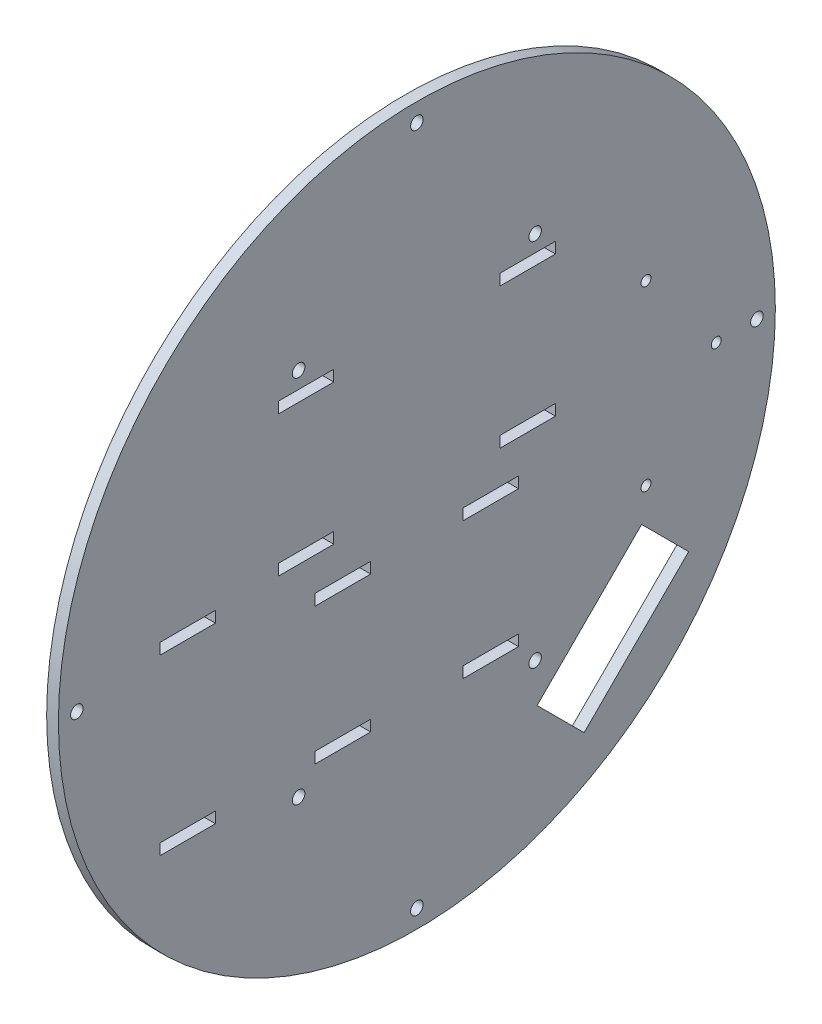
SolidWorks part; units mm, degrees
ref_plane "Front Plane" through (0, 0, 0) normal (0, 0, 1) x (1, 0, 0)
ref_plane "Top Plane" through (0, 0, 0) normal (0, 1, 0) x (1, 0, 0)
ref_plane "Right Plane" through (0, 0, 0) normal (1, 0, 0) x (0, 0, -1)
sketch "Tray Sketch" plane through (0, 0, 0) normal (1, 0, 0) x (0, 0, -1)
  line L0 (32.5269, -60.8112) -> (60.8112, -32.5269)
  line L1 (60.8112, -32.5269) -> (73.5391, -45.2548)
  line L2 (73.5391, -45.2548) -> (45.2548, -73.5391)
  line L3 (45.2548, -73.5391) -> (32.5269, -60.8112)
  line L4 (-22.5, 4.5) -> (-22.5, 7.5)
  line L5 (-22.5, 7.5) -> (-37.5, 7.5)
  line L6 (-37.5, 7.5) -> (-37.5, 4.5)
  line L7 (-37.5, 4.5) -> (-22.5, 4.5)
  line L8 (-22.5, 42.5) -> (-22.5, 45.5)
  line L9 (-22.5, 45.5) -> (-37.5, 45.5)
  line L10 (-37.5, 45.5) -> (-37.5, 42.5)
  line L11 (-37.5, 42.5) -> (-22.5, 42.5)
  line L12 (37.5, 4.5) -> (37.5, 7.5)
  line L13 (37.5, 7.5) -> (22.5, 7.5)
  line L14 (22.5, 7.5) -> (22.5, 4.5)
  line L15 (22.5, 4.5) -> (37.5, 4.5)
  line L16 (37.5, 42.5) -> (37.5, 45.5)
  line L17 (37.5, 45.5) -> (22.5, 45.5)
  line L18 (22.5, 45.5) -> (22.5, 42.5)
  line L19 (22.5, 42.5) -> (37.5, 42.5)
  line L20 (-12.5, -44.5) -> (-12.5, -41.5)
  line L21 (-12.5, -41.5) -> (-27.5, -41.5)
  line L22 (-27.5, -41.5) -> (-27.5, -44.5)
  line L23 (-27.5, -44.5) -> (-12.5, -44.5)
  line L24 (-12.5, -7.5) -> (-12.5, -4.5)
  line L25 (-12.5, -4.5) -> (-27.5, -4.5)
  line L26 (-27.5, -4.5) -> (-27.5, -7.5)
  line L27 (-27.5, -7.5) -> (-12.5, -7.5)
  line L28 (27.5, -44.5) -> (27.5, -41.5)
  line L29 (27.5, -41.5) -> (12.5, -41.5)
  line L30 (12.5, -41.5) -> (12.5, -44.5)
  line L31 (12.5, -44.5) -> (27.5, -44.5)
  line L32 (27.5, -7.5) -> (27.5, -4.5)
  line L33 (27.5, -4.5) -> (12.5, -4.5)
  line L34 (12.5, -4.5) -> (12.5, -7.5)
  line L35 (12.5, -7.5) -> (27.5, -7.5)
  line L36 (-54.5, -45) -> (-54.5, -42)
  line L37 (-54.5, -42) -> (-69.5, -42)
  line L38 (-69.5, -42) -> (-69.5, -45)
  line L39 (-69.5, -45) -> (-54.5, -45)
  line L40 (-54.5, 2) -> (-54.5, 5)
  line L41 (-54.5, 5) -> (-69.5, 5)
  line L42 (-69.5, 5) -> (-69.5, 2)
  line L43 (-69.5, 2) -> (-54.5, 2)
  circle A0 centre (0, 0) radius 97
  circle A1 centre (0, 92) radius 1.7
  circle A2 centre (-92, 0) radius 1.7
  circle A3 centre (0, -92) radius 1.7
  circle A4 centre (92, 0) radius 1.7
  circle A5 centre (32, -50) radius 1.7
  circle A6 centre (-32, -50) radius 1.7
  circle A7 centre (32, 50) radius 1.7
  circle A8 centre (-32, 50) radius 1.7
  circle A9 centre (62, -24) radius 1.35
  circle A10 centre (62, 24) radius 1.35
  circle A11 centre (81, 0) radius 1.35
extrude "Tray" add sketch "Tray Sketch" along normal blind 3.18
ref_axis "Engine Axis" through (3.339, 0, 0) along (-1, 0, 0)
